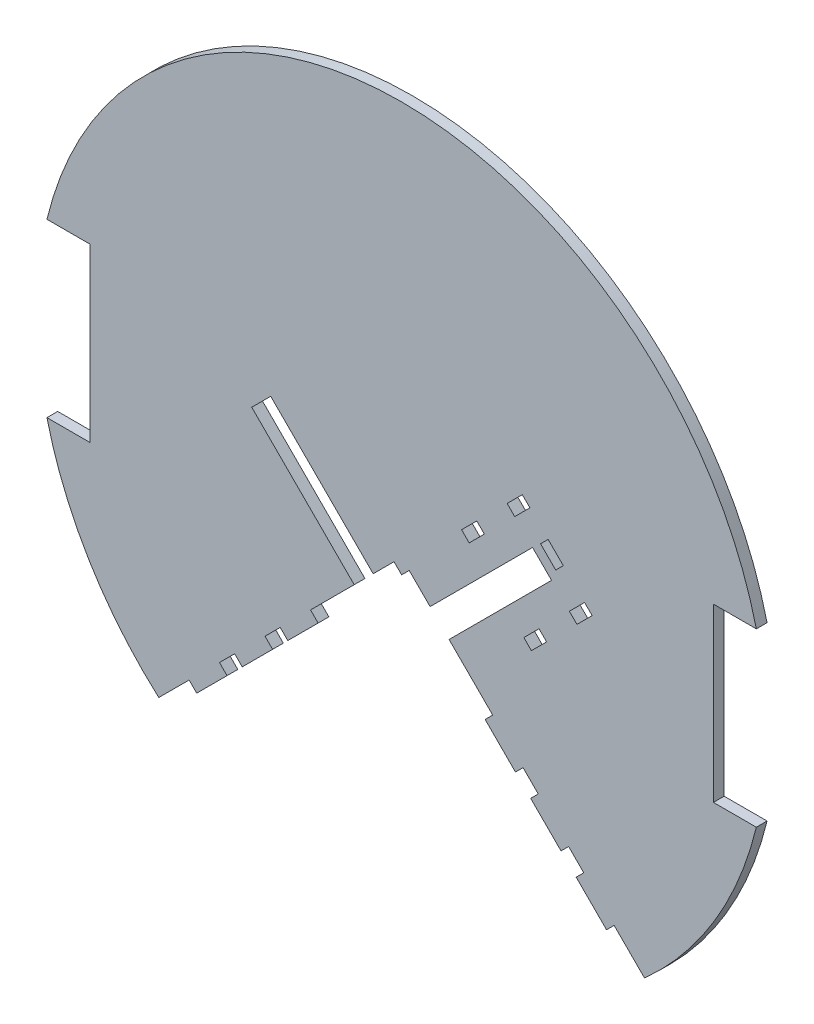
SolidWorks part; units mm, degrees
ref_plane "Front Plane" through (0, 0, 0) normal (0, 0, 1) x (1, 0, 0)
ref_plane "Top Plane" through (0, 0, 0) normal (0, 1, 0) x (1, 0, 0)
ref_plane "Right Plane" through (0, 0, 0) normal (1, 0, 0) x (0, 0, -1)
sketch "Sketch1" plane through (0, 0, 0) normal (0, 0, 1) x (1, 0, 0)
  circle A0 centre (0, 0) radius 215.9
  dimension "D1" = 431.8
extrude "Base Plate Extrusion" add sketch "Sketch1" along normal blind 6.35
sketch "Sketch2" plane through (0, 0, 6.35) normal (0, 0, 1) x (1, 0, 0)
  line L0 (0, 0) -> (0, -230.9791) construction
  line L1 (0, -17.4608) -> (143.6841, -161.1449)
  line L2 (0, -17.4608) -> (-143.6841, -161.1449)
  circle A1 centre (0, 0) radius 215.9 construction
  arc A2 (143.6841, -161.1449) -> (-143.6841, -161.1449) centre (0, 0) cw
  dimension "D1" = 90
  dimension "D2" = 203.2
extrude "V Funnel Cut" cut sketch "Sketch2" against normal through all
sketch "Sketch3" plane through (0, 0, 6.35) normal (0, 0, 1) x (1, 0, 0)
  line L0 (0, 0) -> (251.7982, 0) construction
  line L1 (209.8384, 50.8) -> (184.4384, 50.8)
  line L2 (209.8384, 50.8) -> (209.8384, -50.8)
  line L3 (209.8384, -50.8) -> (184.4384, -50.8)
  line L4 (184.4384, 50.8) -> (184.4384, -50.8)
  arc A0 (143.6841, -161.1449) -> (-143.6841, -161.1449) centre (0, 0) ccw construction
  arc A1 (209.8384, 50.8) -> (209.8384, -50.8) centre (0, 0) cw
  arc M7 (143.6841, -161.1449) -> (-143.6841, -161.1449) centre (0, 0) ccw
  dimension "D1" = 25.4
  dimension "D2" = 101.6
extrude "Wheel Track Cut" cut sketch "Sketch3" against normal through all contours L2 L0 A1 | L4 L0 L2 L1 | L0 L4 L3 L2 | L0 L2 M7 region at (197.1384, 25.4, 6.35) region at (197.1384, -25.4, 6.35) region at (212.266, 19.0862, 6.35) region at (212.266, -19.0862, 6.35)
mirror "Wheel Track Cut Mirror" about plane through (0, 0, 0) normal (1, 0, 0) of "Wheel Track Cut"
sketch "Sketch4" plane through (0, 0, 6.35) normal (0, 0, 1) x (1, 0, 0)
  line L0 (88.68, 15.0926) -> (77.4547, 26.3179)
  line L1 (88.68, 15.0926) -> (28.0633, -45.5241)
  line L2 (77.4547, 26.3179) -> (16.838, -34.2988)
  line L3 (28.0633, -45.5241) -> (16.838, -34.2988)
  line L4 (84.3174, 21.9553) -> (56.956, -5.4061) construction
  line L5 (65.1069, -1.7454) -> (69.5826, 2.7303) construction
  line L6 (65.0924, 7.2204) -> (60.6167, 2.7447) construction
  line L7 (143.6841, -161.1449) -> (0, -17.4608) construction
  dimension "D1" = 15.875
  dimension "D2" = 85.725
extrude "Cut-Extrude3" cut sketch "Sketch4" against normal through all
sketch "Sketch5" plane through (0, 0, 6.35) normal (0, 0, 1) x (1, 0, 0)
  line L0 (-4.4901, -21.951) -> (0, -17.4608)
  line L1 (-4.4901, -21.951) -> (0, -26.4411)
  line L2 (0, -17.4608) -> (4.4901, -21.951)
  line L3 (0, -26.4411) -> (4.4901, -21.951)
  line L4 (0, -17.4608) -> (-143.6841, -161.1449) construction
  line L6 (4.4901, -21.951) -> (0, -26.4411) construction
  dimension "D1" = 6.35
extrude "Boss-Extrude2" add sketch "Sketch5" against normal up to surface (6.35 mm away) up to face at (14.0691, -14.8765, 0)
mirror "Mirror2" about plane through (0, 0, 0) normal (1, 0, 0) of "Cut-Extrude3"
sketch "Sketch6" plane through (8.7304, -8.7304, 0) normal (0.7071, -0.7071, 0) x (0, 0, -1)
  line L0 (-6.35, -52.0342) -> (-6.35, -215.5467) construction
  line L1 (-6.35, -190.1467) -> (0, -190.1467)
  line L2 (-6.35, -190.1467) -> (-6.35, -164.7467)
  line L3 (-6.35, -164.7467) -> (0, -164.7467)
  line L4 (0, -190.1467) -> (0, -164.7467)
  line L5 (0, -52.0342) -> (0, -215.5467) construction
  dimension "D1" = 25.4
  dimension "D2" = 25.4
extrude "Boss-Extrude3" add sketch "Sketch6" along normal blind 6.35
pattern_linear "LPattern1" count 3 spacing 38.1 along (0.7071, 0.7071, 0) of "Boss-Extrude3"
sketch "Sketch7" plane through (-8.7304, -8.7304, 0) normal (-0.7071, -0.7071, 0) x (0, 0, 1)
  line L0 (6.35, -215.5467) -> (6.35, -52.0342) construction
  line L1 (6.35, -164.7467) -> (0, -164.7467)
  line L2 (6.35, -164.7467) -> (6.35, -190.1467)
  line L3 (6.35, -190.1467) -> (0, -190.1467)
  line L4 (0, -164.7467) -> (0, -190.1467)
  line L5 (0, -215.5467) -> (0, -52.0342) construction
  dimension "D1" = 25.4
  dimension "D2" = 25.4
extrude "Boss-Extrude4" add sketch "Sketch7" along normal blind 6.35
pattern_linear "LPattern2" count 3 spacing 38.1 along (-0.7071, 0.7071, 0) of "Boss-Extrude4"
sketch "Sketch8" plane through (0, 0, 0) normal (0, 0, -1) x (-1, 0, 0)
  line L0 (-72.2911, -22.4) -> (-81.2713, -13.4197)
  line L1 (-81.2713, -13.4197) -> (-85.7614, -17.9098)
  line L2 (-85.7614, -17.9098) -> (-76.7812, -26.8901)
  line L3 (-76.7812, -26.8901) -> (-72.2911, -22.4)
  line L4 (-99.2318, 4.5408) -> (-103.722, 0.0507)
  line L5 (-103.722, 0.0507) -> (-112.7022, 9.0309)
  line L6 (-112.7022, 9.0309) -> (-108.2121, 13.521)
  line L7 (-108.2121, 13.521) -> (-99.2318, 4.5408)
  line L8 (-95.6515, 26.0817) -> (-86.6712, 35.0619)
  line L9 (-86.6712, 35.0619) -> (-82.1811, 30.5718)
  line L10 (-82.1811, 30.5718) -> (-91.1613, 21.5915)
  line L11 (-91.1613, 21.5915) -> (-95.6515, 26.0817)
  line L12 (-66.9029, 36.8697) -> (-62.4128, 41.3598)
  line L13 (-62.4128, 41.3598) -> (-71.393, 50.3401)
  line L14 (-71.393, 50.3401) -> (-75.8832, 45.85)
  line L15 (-75.8832, 45.85) -> (-66.9029, 36.8697)
  line L16 (-48.9424, 18.9092) -> (-44.4523, 23.3993)
  line L17 (-44.4523, 23.3993) -> (-35.472, 14.4191)
  line L18 (-35.472, 14.4191) -> (-39.9621, 9.9289)
  line L19 (-39.9621, 9.9289) -> (-48.9424, 18.9092)
extrude "Cut-Extrude4" cut sketch "Sketch8" against normal blind 6.35
